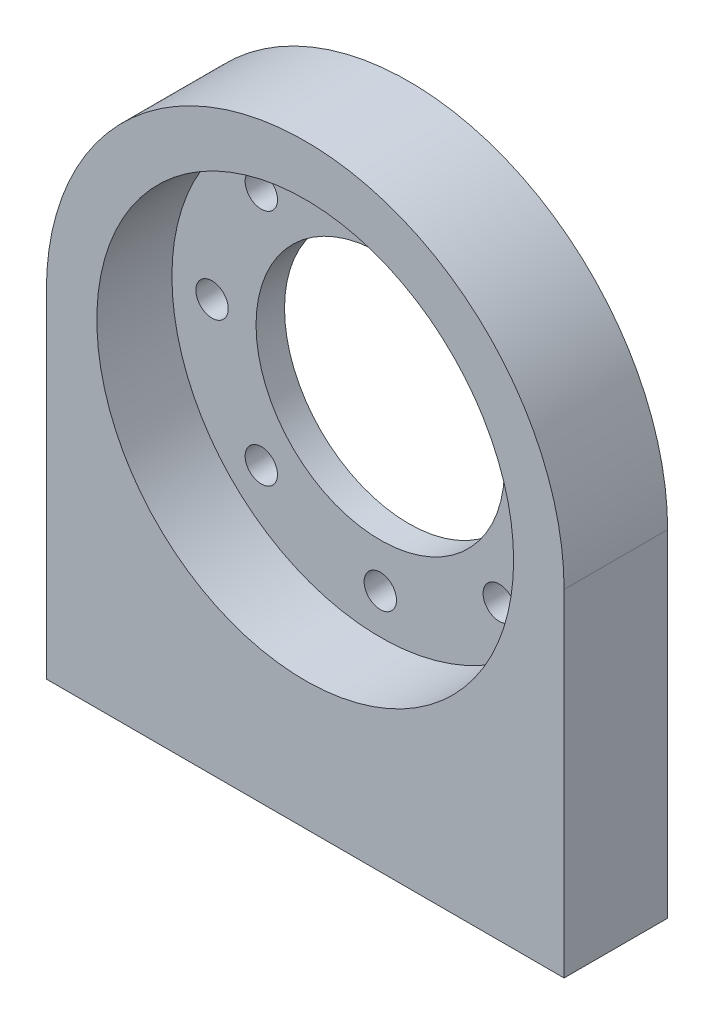
SolidWorks part; units mm, degrees
ref_plane "Plan de face" through (0, 0, 0) normal (0, 0, 1) x (1, 0, 0)
ref_plane "Plan de dessus" through (0, 0, 0) normal (0, 1, 0) x (1, 0, 0)
ref_plane "Plan de droite" through (0, 0, 0) normal (1, 0, 0) x (0, 0, -1)
sketch "Esquisse1" plane through (0, 0, 0) normal (0, 0, 1) x (1, 0, 0)
  line L1 (-20, 0) -> (20, 0) construction
  line L2 (-20, 0) -> (-20, -26)
  line L3 (-20, -26) -> (20, -26)
  line L4 (20, 0) -> (20, -26)
  circle A0 centre (0, 0) radius 20 construction
  arc A1 (-20, 0) -> (20, 0) centre (0, 0) cw
  circle A2 centre (0, 0) radius 9.6
  dimension "D1" = 40
  dimension "D3" = 19.2
  dimension "D2" = 26
extrude "Boss.-Extru.1" add sketch "Esquisse1" along normal blind 8
sketch "Esquisse2" plane through (0, 0, 8) normal (0, 0, 1) x (1, 0, 0)
  circle A0 centre (0, 0) radius 16.1
  dimension "D1" = 32.2
extrude "Enlèv. mat.-Extru.1" cut sketch "Esquisse2" against normal offset from surface (5.8 mm away) 2.2 up to face at (0, -8, 0)
sketch "Esquisse3" plane through (0, 0, 0) normal (0, 0, -1) x (-1, 0, 0)
  line L0 (0, 13) -> (0, 0) construction
  circle A0 centre (0, 13) radius 1.25
  circle A1 centre (9.1924, 9.1924) radius 1.25
  circle A2 centre (13, 0) radius 1.25
  circle A3 centre (9.1924, -9.1924) radius 1.25
  circle A4 centre (0, -13) radius 1.25
  circle A5 centre (-9.1924, -9.1924) radius 1.25
  circle A6 centre (-13, 0) radius 1.25
  circle A7 centre (-9.1924, 9.1924) radius 1.25
  point P17 (0, 0)
  dimension "D1" = 2.5
  dimension "D2" = 13
  dimension "D3" = 8
extrude "Enlèv. mat.-Extru.2" cut sketch "Esquisse3" against normal up to next
sketch "Esquisse4" plane through (0, -26, 0) normal (0, -1, 0) x (1, 0, 0)
  line L0 (0, 0) -> (0, 8) construction
  line L1 (-20, 0) -> (20, 0) construction
  line L2 (-20, 8) -> (20, 8) construction
  line L3 (-16, 4) -> (16, 4) construction
  line L4 (-20, 8) -> (-20, 0) construction
  circle A0 centre (-16, 4) radius 1.5
  circle A1 centre (16, 4) radius 1.5
  point P9 (0, 4)
  dimension "D2" = 3
  dimension "D1" = 4
extrude "Enlèv. mat.-Extru.3" cut sketch "Esquisse4" against normal blind 15
